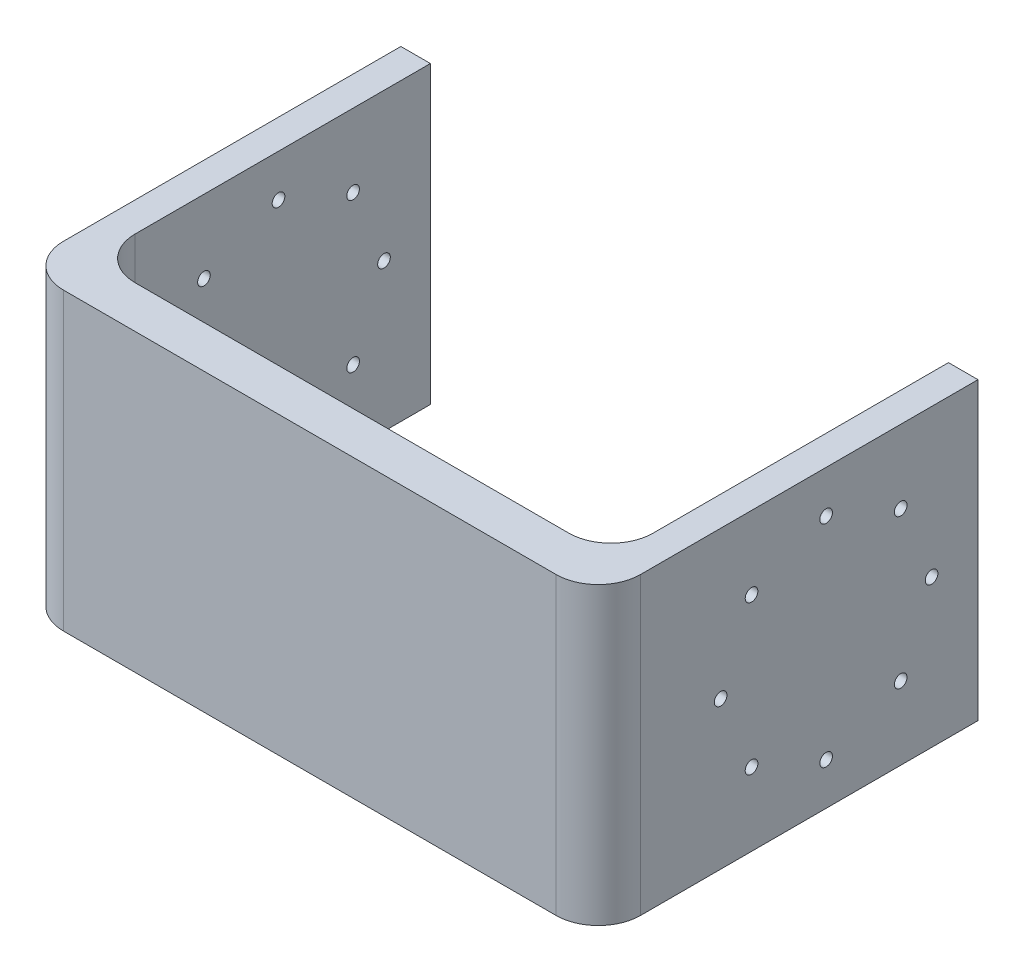
SolidWorks part; units mm, degrees
material "PPE"
ref_plane "Front Plane" through (0, 0, 0) normal (0, 0, 1) x (1, 0, 0)
ref_plane "Top Plane" through (0, 0, 0) normal (0, 1, 0) x (1, 0, 0)
ref_plane "Right Plane" through (0, 0, 0) normal (1, 0, 0) x (0, 0, -1)
sketch "Sketch1" plane through (0, 0, 0) normal (0, 1, 0) x (1, 0, 0)
  line L0 (-29.2, 0) -> (29.2, 0)
  line L1 (34.2, 5) -> (34.2, 45)
  line L2 (34.2, 45) -> (30.7, 45)
  line L3 (-30.7, 45) -> (-30.7, 10)
  line L5 (-25.7, 5) -> (25.7, 5)
  line L6 (-30.7, 45) -> (-34.2, 45)
  line L7 (-34.2, 45) -> (-34.2, 5)
  line L8 (30.7, 10) -> (30.7, 45)
  arc A0 (25.7, 5) -> (30.7, 10) centre (25.7, 10) ccw
  arc A1 (29.2, 0) -> (34.2, 5) centre (29.2, 5) ccw
  arc A2 (-30.7, 10) -> (-25.7, 5) centre (-25.7, 10) ccw
  arc A3 (-34.2, 5) -> (-29.2, 0) centre (-29.2, 5) ccw
  point P0 (0, 0)
  point P12 (27.4523, -6.6651)
  point P13 (30.7, 5)
  point P16 (34.2, 0)
  point P19 (-30.7, 5)
  point P22 (-34.2, 0)
  dimension "D5" = 5
  dimension "D1" = 68.4
  dimension "D2" = 61.4
  dimension "D3" = 40
  dimension "D4" = 45
extrude "Boss-Extrude1" add sketch "Sketch1" along normal mid plane 35
sketch "Sketch2" plane through (-34.2, 0, 0) normal (-1, 0, 0) x (0, 0, 1)
  line L1 (-45, 17.5) -> (-45, -17.5) construction
  line L2 (-39.5, 0) -> (-14.5, 0) construction
  line L6 (-27, 12.5) -> (-27, -12.5) construction
  circle A0 centre (-27, 0) radius 15
  circle A1 centre (-27, 0) radius 12.5
  circle A2 centre (-27, 12.5) radius 0.75
  circle A3 centre (-18.1612, 8.8388) radius 0.75
  circle A4 centre (-27, 0) radius 12.5
  circle A5 centre (-14.5, 0) radius 0.75
  circle A6 centre (-27, 0) radius 12.5
  circle A7 centre (-18.1612, -8.8388) radius 0.75
  circle A8 centre (-27, 0) radius 12.5
  circle A9 centre (-27, -12.5) radius 0.75
  circle A10 centre (-27, 0) radius 12.5
  circle A11 centre (-35.8388, -8.8388) radius 0.75
  circle A12 centre (-27, 0) radius 12.5
  circle A13 centre (-39.5, 0) radius 0.75
  circle A14 centre (-27, 0) radius 12.5
  circle A15 centre (-35.8388, 8.8388) radius 0.75
  circle A16 centre (-27, 0) radius 12.5
  circle A17 centre (-27, -12.5) radius 0.75 [skipped]
  point P8 (-45, 0)
  point P44 (-27, 0)
  dimension "D1" = 30
  dimension "D2" = 25
  dimension "D3" = 1.5
  dimension "D4" = 8
  dimension "D5" = 18
  dimension "D6" = 1.5
extrude "Cut-Extrude1" cut sketch "Sketch2" against normal up to surface (68.4 mm away) contours A1 A2 | A14 A15 | A14 A15 | A2 | A13 | A11 | A7 | A5 | A3 region at (-34.2, 12.8142, -27) region at (-34.2, 8.6109, -35.6109) region at (-34.2, 9.061, -36.061) up to face at (34.2, 0, -25)
extrude "Cut-Extrude2" cut sketch "Sketch2<3>" against normal through all contours A9
sketch "Sketch2<3>" plane through (-34.2, 0, 0) normal (-1, 0, 0) x (0, 0, 1) same geometry as "Sketch2"
